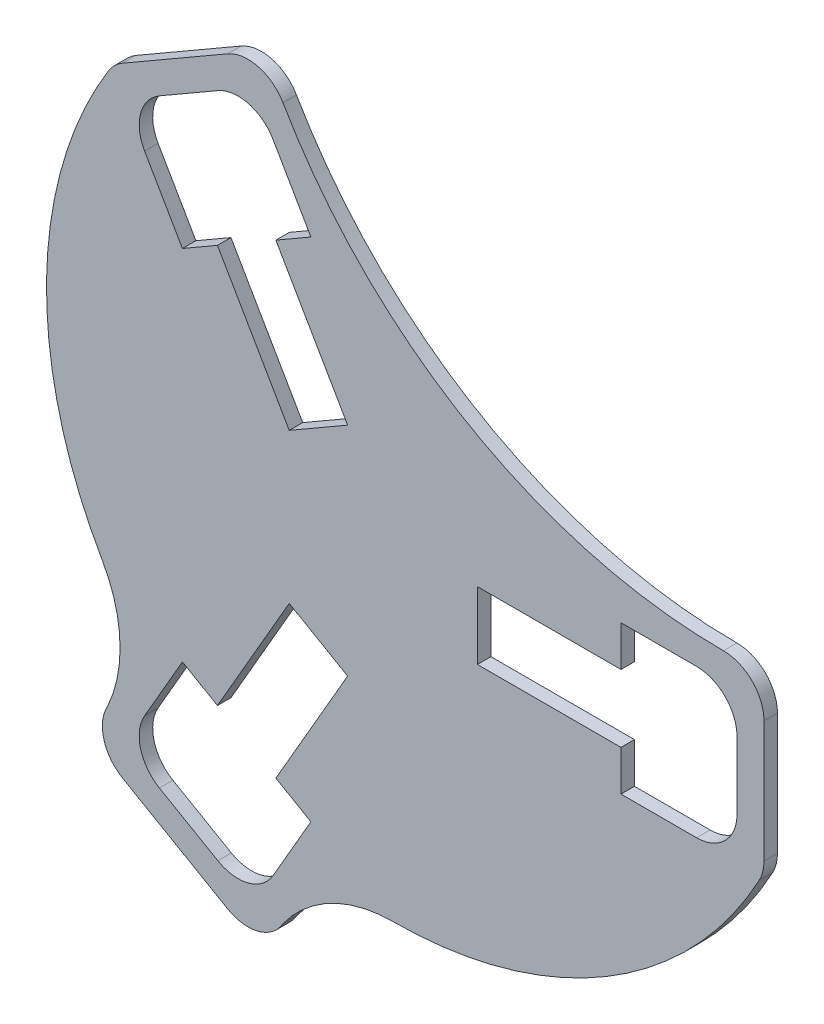
SolidWorks part; units mm, degrees
ref_plane "Front Plane" through (0, 0, 0) normal (0, 0, 1) x (1, 0, 0)
ref_plane "Top Plane" through (0, 0, 0) normal (0, 1, 0) x (1, 0, 0)
ref_plane "Right Plane" through (0, 0, 0) normal (1, 0, 0) x (0, 0, -1)
sketch "Sketch1" plane through (0, 0, 0) normal (0, 0, 1) x (1, 0, 0)
  line L0 (-8.8184, -40.2739) -> (-43.8184, -100.8957)
  line L1 (39.2875, -12.5) -> (109.2875, -12.5)
  line L2 (39.2875, -12.5) -> (39.2875, 12.5)
  line L3 (39.2875, 12.5) -> (109.2875, 12.5)
  line L4 (39.2875, 0) -> (0, 0) construction
  line L5 (39.2875, -12.5) -> (109.2875, 12.5) construction
  line L6 (39.2875, 12.5) -> (109.2875, -12.5) construction
  line L7 (-30.4691, -27.7739) -> (-8.8184, -40.2739)
  line L8 (-30.4691, -27.7739) -> (-65.4691, -88.3957)
  line L9 (-30.4691, 27.7739) -> (-65.4691, 88.3957)
  line L10 (-8.8184, 40.2739) -> (-30.4691, 27.7739)
  line L11 (-8.8184, 40.2739) -> (-43.8184, 100.8957)
  arc A0 (-43.8184, -100.8957) -> (109.2875, -12.5) centre (0, 0) ccw
  arc A1 (-65.4691, 88.3957) -> (-65.4691, -88.3957) centre (0, 0) ccw
  arc A2 (109.2875, 12.5) -> (-43.8184, 100.8957) centre (0, 0) ccw
  point P4 (74.2875, 0)
  dimension "D4" = 110
  dimension "D1" = 70
  dimension "D2" = 25
  dimension "D3" = 3
extrude "Boss-Extrude1" add sketch "Sketch1" along normal blind 5
sketch "Sketch3" plane through (0, 0, 5) normal (0, 0, 1) x (1, 0, 0)
  line L0 (145.507, -22.5) -> (145.507, 22.5)
  line L1 (130.507, 37.5) -> (96.507, 37.5)
  line L2 (96.507, -37.5) -> (96.507, 37.5)
  line L3 (130.507, -37.5) -> (96.507, -37.5)
  line L4 (145.507, -37.5) -> (145.507, 37.5) construction
  line L5 (145.507, -37.5) -> (96.507, -37.5) construction
  line L6 (145.507, 37.5) -> (96.507, 37.5) construction
  line L7 (120.507, -27.5) -> (106.507, -27.5)
  line L8 (135.507, -12.5) -> (135.507, 12.5)
  line L9 (120.507, 27.5) -> (106.507, 27.5)
  line L10 (106.507, -27.5) -> (106.507, 27.5)
  line L11 (135.507, -27.5) -> (106.507, 27.5) construction
  line L12 (135.507, 27.5) -> (106.507, -27.5) construction
  line L13 (135.507, -27.5) -> (135.507, 27.5) construction
  line L14 (135.507, -27.5) -> (106.507, -27.5) construction
  line L15 (135.507, 27.5) -> (106.507, 27.5) construction
  arc A1 (-43.8184, -100.8957) -> (109.2875, -12.5) centre (0, 0) ccw construction
  arc A2 (145.507, -22.5) -> (130.507, -37.5) centre (130.507, -22.5) cw
  arc A3 (145.507, 22.5) -> (130.507, 37.5) centre (130.507, 22.5) ccw
  arc A4 (135.507, -12.5) -> (120.507, -27.5) centre (120.507, -12.5) cw
  arc A5 (135.507, 12.5) -> (120.507, 27.5) centre (120.507, 12.5) ccw
  point P0 (121.007, 0)
  point P8 (121.007, 0)
  dimension "D4" = 15
  dimension "D1" = 29
  dimension "D2" = 55
  dimension "D3" = 10
extrude "Boss-Extrude2" add sketch "Sketch3" against normal blind 5
sketch "Sketch4" plane through (0, 0, 5) normal (0, 0, 1) x (1, 0, 0)
  line L0 (106.507, 12.5) -> (106.507, -12.5) construction
  line L1 (120.507, -27.5) -> (92.507, -27.5)
  line L2 (120.507, -27.5) -> (120.507, 27.5)
  line L3 (120.507, 27.5) -> (92.507, 27.5)
  line L4 (92.507, -27.5) -> (92.507, 27.5)
  line L5 (120.507, -27.5) -> (92.507, 27.5) construction
  line L6 (120.507, 27.5) -> (92.507, -27.5) construction
  line L7 (120.507, 27.5) -> (106.507, 27.5) construction
  line L8 (135.507, -12.5) -> (135.507, 12.5) construction
  point P0 (106.507, 0)
  dimension "D1" = 43
extrude "Cut-Extrude1" cut sketch "Sketch4" against normal blind 5
pattern_circular "CirPattern1" count 3 over 360 about axis through (0, 0, 5) along (0, 0, 1) of "Cut-Extrude1", "Boss-Extrude2"
sketch "Sketch5" plane through (0, 0, 5) normal (0, 0, 1) x (1, 0, 0)
  circle A0 centre (130.507, 226.0448) radius 188.5448
  line M33 (130.507, 37.5) -> (103.4106, 37.5)
  arc M34 (103.4106, 37.5) -> (-19.2293, 108.3062) centre (0, 0) ccw
  line M35 (-19.2293, 108.3062) -> (-32.7776, 131.7724)
extrude "Cut-Extrude2" cut sketch "Sketch5" against normal blind 5
extrude "Boss-Extrude3" add sketch "Sketch5<2>" against normal blind 5 contours A0 M35 M34 | A0 M34 M33 region at (-21.9348, 114.2274, 5) region at (109.8913, 38.1176, 5)
sketch "Sketch5<2>" plane through (0, 0, 5) normal (0, 0, 1) x (1, 0, 0) same geometry as "Sketch5"
sketch "Sketch6" plane through (0, 0, 5) normal (0, 0, 1) x (1, 0, 0)
  circle A0 centre (34.0533, 28.6428) radius 154.4976
  circle A1 centre (7.7787, 43.8124) radius 154.4976
  circle A2 centre (-143.165, -73.4011) radius 50
  arc A3 (-19.2293, -108.3062) -> (103.4106, -37.5) centre (0, 0) ccw construction
  arc A4 (-84.1812, 70.8062) -> (-84.1812, -70.8062) centre (0, 0) ccw construction
  circle A5 centre (8.0153, -160.685) radius 50
  arc A6 (-92.2391, 114.7628) -> (-97.7295, 94.2724) centre (-84.7391, 101.7724) ccw construction
  arc A7 (130.507, -37.5) -> (145.507, -22.5) centre (130.507, -22.5) ccw construction
  arc M5 (-92.2391, 114.7628) -> (-97.7295, 94.2724) centre (-84.7391, 101.7724) ccw
  line M6 (-97.7295, 94.2724) -> (-84.1812, 70.8062)
  arc M7 (-84.1812, 70.8062) -> (-84.1812, -70.8062) centre (0, 0) ccw
  line M8 (-84.1812, -70.8062) -> (-97.7295, -94.2724)
  line M12 (-32.7776, -131.7724) -> (-19.2293, -108.3062)
  arc M13 (-19.2293, -108.3062) -> (103.4106, -37.5) centre (0, 0) ccw
  line M14 (103.4106, -37.5) -> (130.507, -37.5)
  arc M15 (130.507, -37.5) -> (145.507, -22.5) centre (130.507, -22.5) ccw
  dimension "D1" = 100
  dimension "D2" = 100
extrude "Boss-Extrude4" add sketch "Sketch6" against normal blind 5 contours A0 M13 M15 M14 | A0 M5 M7 M6 | A2 A1 A0 M8 | A2 A1 M8 | A1 A0 M12 | A0 M13 M12 | A0 M12 region at (-106.7397, 46.6006, 5) region at (-23.8874, -120.3012, 5) region at (-13.537, -112.3371, 5) region at (93.7272, -69.139, 5) region at (-90.5182, -67.8919, 5) region at (-92.2402, -80.8377, 5)
